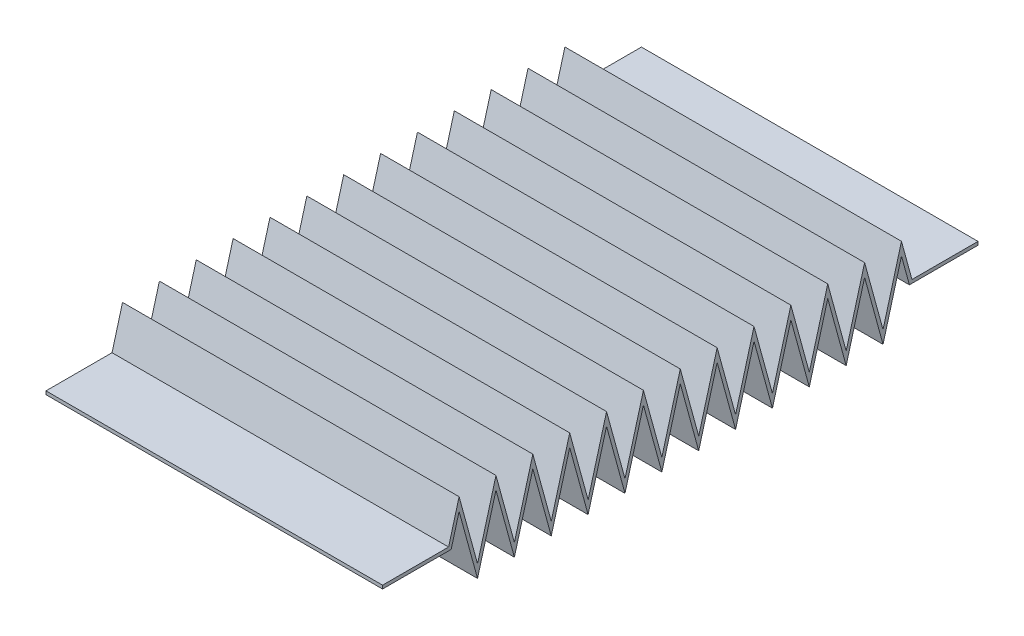
SolidWorks part; units mm, degrees
ref_plane "Front Plane" through (0, 0, 0) normal (0, 0, 1) x (1, 0, 0)
ref_plane "Top Plane" through (0, 0, 0) normal (0, 1, 0) x (1, 0, 0)
ref_plane "Right Plane" through (0, 0, 0) normal (1, 0, 0) x (0, 0, -1)
sketch "Sketch2" plane through (0, 0, 0) normal (0, 0, 1) x (1, 0, 0)
  line L1 (-27.5, 10) -> (27.5, 10)
  line L2 (-27.5, 10) -> (-27.5, 0)
  line L3 (-27.5, 0) -> (27.5, 0)
  line L4 (27.5, 10) -> (27.5, 0)
  point P4 (0, 0)
  dimension "D1" = 10
  dimension "D2" = 55
sketch "Sketch3" plane through (0, 0, 0) normal (1, 0, 0) x (0, 0, -1)
  line L0 (0, 10) -> (88.4572, 10) construction
  line L1 (0, 0) -> (88.4572, 0) construction
  line L3 (10, 5) -> (11.3691, 10)
  line L4 (11.3691, 10) -> (14.1074, 0)
  line L5 (14.1074, 0) -> (16.8457, 10)
  line L6 (16.8457, 10) -> (19.584, 0)
  line L7 (19.584, 0) -> (22.3223, 10)
  line L8 (22.3223, 10) -> (25.0606, 0)
  line L9 (25.0606, 0) -> (27.7989, 10)
  line L10 (27.7989, 10) -> (30.5372, 0)
  line L11 (30.5372, 0) -> (33.2754, 10)
  line L12 (33.2754, 10) -> (36.0137, 0)
  line L13 (36.0137, 0) -> (38.752, 10)
  line L14 (38.752, 10) -> (41.4903, 0)
  line L15 (41.4903, 0) -> (44.2286, 10)
  line L16 (44.2286, 10) -> (46.9669, 0)
  line L17 (46.9669, 0) -> (49.7052, 10)
  line L18 (49.7052, 10) -> (52.4435, 0)
  line L19 (0, 10) -> (0, 0) construction
  line L20 (52.4435, 0) -> (55.1817, 10)
  line L21 (55.1817, 10) -> (57.92, 0)
  line L22 (57.92, 0) -> (60.6583, 10)
  line L23 (60.6583, 10) -> (63.3966, 0)
  line L24 (63.3966, 0) -> (66.1349, 10)
  line L25 (66.1349, 10) -> (68.8732, 0)
  line L26 (68.8732, 0) -> (71.6115, 10)
  line L27 (71.6115, 10) -> (74.3497, 0)
  line L28 (74.3497, 0) -> (77.088, 10)
  line L29 (77.088, 10) -> (78.4572, 5)
  line L30 (88.4572, 10) -> (88.4572, 0) construction
  line L31 (10, 5) -> (0, 5)
  line L32 (78.4572, 5) -> (88.4572, 5)
  line L34 (88.4572, 22.75) -> (88.4572, 4.75) construction
  dimension "D2" = 10
  dimension "D1" = 10
  dimension "D3" = 10
extrude "Extrude-Thin1" add sketch "Sketch3" against normal mid plane 50 thin thin type mid plane wall 0.5
